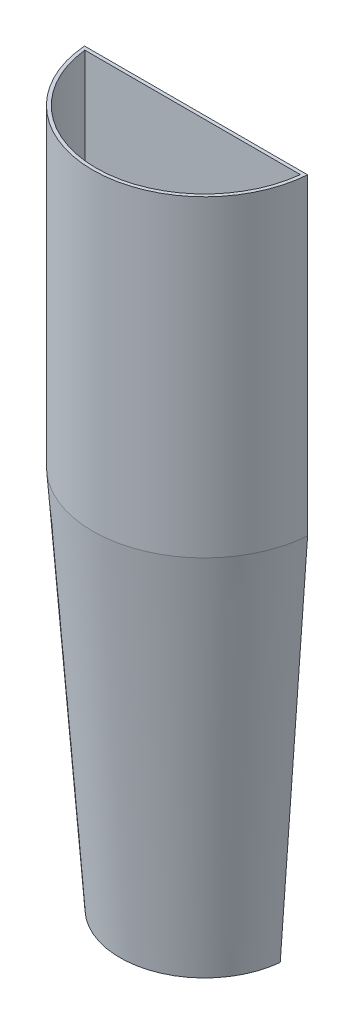
SolidWorks part; units mm, degrees
material "ABS PC"
ref_plane "Front Plane" through (0, 0, 0) normal (0, 0, 1) x (1, 0, 0)
ref_plane "Top Plane" through (0, 0, 0) normal (0, 1, 0) x (1, 0, 0)
ref_plane "Right Plane" through (0, 0, 0) normal (1, 0, 0) x (0, 0, -1)
sketch "Body Sketch" plane through (0, 0, 0) normal (0, 0, 1) x (1, 0, 0)
  line L0 (-31.7, 0) -> (-31.7, 91.39)
  line L1 (0, 91.39) -> (0, 0)
  line L2 (-31.7, 91.39) -> (0, 91.39)
  line L3 (-31.7, 0) -> (0, 0)
  line L4 (-31.7, 0) -> (-23.8, -111)
  line L5 (-23.8, -111) -> (0, -111)
  line L6 (0, 0) -> (0, -111)
  dimension "D1" = 91.39
  dimension "D2" = 23.8
  dimension "D3" = 31.7
  dimension "D4" = 111.2808
revolve "Upper Body Revolve" add sketch "Body Sketch" angle 180 about L1 region at (-15.85, 45.695, 0) reverse direction yes
revolve "Lower Body Revolve" add sketch "Sketch1<35>" angle 180 about L6 region at (-13.9687, -52.8667, 0) reverse direction yes
sketch "Sketch1<35>" plane through (0, 0, 0) normal (0, 0, 1) x (1, 0, 0) same geometry as "Body Sketch"
sketch "Centre Cut Sketch" plane through (0, 91.39, 0) normal (0, 1, 0) x (1, 0, 0)
  line L0 (31.7, 0) -> (-31.7, 0)
  line L2 (-31.7, 0) -> (-31.7, -3.5)
  line L3 (-31.7, -3.5) -> (31.7, -3.5)
  line L4 (31.7, -3.5) -> (31.7, 0)
  dimension "D1" = 3.5
extrude "Centre Cut Extrude" cut sketch "Centre Cut Sketch" against normal through all
shell "Body Shell" thickness 1 removed face at (0, 91.39, 17.6) outward yes
